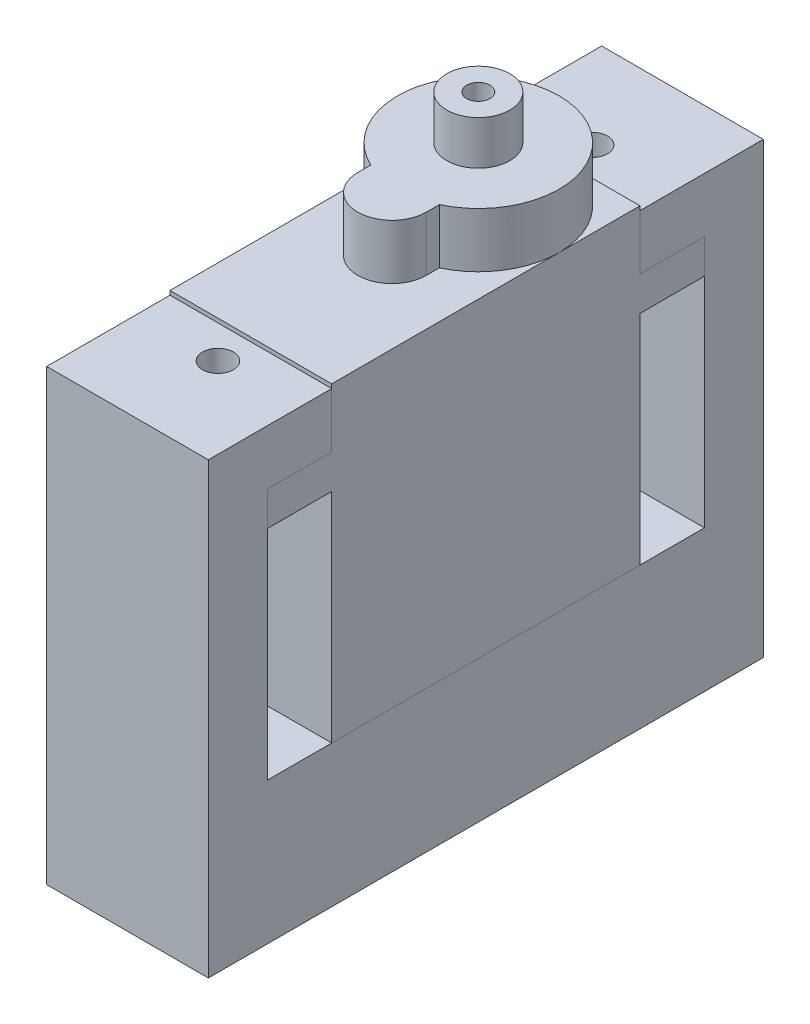
SolidWorks part; units mm, degrees
ref_plane "Plan de face" through (0, 0, 0) normal (0, 0, 1) x (1, 0, 0)
ref_plane "Plan de dessus" through (0, 0, 0) normal (0, 1, 0) x (1, 0, 0)
ref_plane "Plan de droite" through (0, 0, 0) normal (1, 0, 0) x (0, 0, -1)
sketch "Esquisse1" plane through (0, 0, 0) normal (1, 0, 0) x (0, 0, -1)
  line L0 (11.25, 0) -> (-11.25, 0) construction
  line L1 (0, 14.95) -> (0, -14.95) construction
  line L2 (-11.25, -14.95) -> (11.25, -14.95)
  line L3 (11.25, -14.95) -> (11.25, 0.95)
  line L4 (11.25, 0.95) -> (15.95, 0.95)
  line L5 (15.95, 0.95) -> (15.95, 3.45)
  line L6 (15.95, 3.45) -> (11.25, 3.45)
  line L7 (11.25, 3.45) -> (11.25, 7.75)
  line L8 (11.25, 7.75) -> (-11.25, 7.75)
  line L9 (-11.25, 7.75) -> (-11.25, 3.45)
  line L10 (-11.25, 3.45) -> (-15.95, 3.45)
  line L11 (-15.95, 3.45) -> (-15.95, 0.95)
  line L12 (-15.95, 0.95) -> (-11.25, 0.95)
  line L13 (-11.25, 0.95) -> (-11.25, -14.95)
  point P4 (0, 0)
  point P8 (0, 0)
  dimension "D1" = 15.9
  dimension "D2" = 2.5
  dimension "D3" = 4.7
  dimension "D4" = 22.5
  dimension "D5" = 4.7
  dimension "D6" = 4.3
  dimension "D7" = 2.5
  dimension "D8" = 15.9
  dimension "D9" = 22.5
  dimension "D10" = 18.4
  dimension "D11" = 22.7
extrude "Boss.-Extru.1" add sketch "Esquisse1" along normal blind 5.9 and the other way blind 5.9
sketch "Esquisse2" plane through (0, 7.75, 0) normal (0, 1, 0) x (1, 0, 0)
  line L0 (-5.9, 11.25) -> (5.9, 11.25) construction
  line L1 (-5.9, 11.25) -> (5.9, 11.25) construction
  line L2 (-2.5, 0.0058) -> (2.5, 0.0058) construction
  line L3 (0, 5.35) -> (0, -3.45) construction
  line L4 (-2.5, 0.0058) -> (-2.5, -3.45) construction
  line L5 (-2.5, -3.45) -> (2.5, -3.45) construction
  line L6 (2.5, -3.45) -> (2.5, 0.0058) construction
  line L7 (-2.5, -0.95) -> (-2.5, 0.0058)
  line L8 (2.5, -0.95) -> (2.5, 0.0058)
  arc A0 (2.5, 0.0058) -> (-2.5, 0.0058) centre (0, 5.35) ccw
  arc A1 (-2.5, -0.95) -> (2.5, -0.95) centre (0, -0.95) ccw
  point P6 (-2.5, -1.7221)
  point P11 (2.5, -1.7221)
extrude "Boss.-Extru.2" add sketch "Esquisse2" along normal blind 4
sketch "Esquisse3" plane through (0, 3.45, 0) normal (0, 1, 0) x (1, 0, 0)
  line L0 (0, 18.25) -> (0, 11.25) construction
  line L1 (0, 11.25) -> (7.0868, 11.25) construction
  line L2 (0, 15.95) -> (0, 13.65) construction
  line L3 (-5.9, 15.95) -> (5.9, 15.95) construction
  line L4 (-0.65, 15.95) -> (0.65, 15.95) construction
  line L5 (-0.65, 15.95) -> (-0.65, 14.4099)
  line L6 (0.65, 15.95) -> (0.65, 14.4099)
  line L7 (-0.65, 15.95) -> (0.65, 15.95)
  line L8 (0, 0) -> (11.6221, 0) construction
  line L9 (-0.65, -15.95) -> (0.65, -15.95) construction
  line L10 (0, -15.95) -> (0, -13.65) construction
  line L11 (0, -11.25) -> (7.0868, -11.25) construction
  line L12 (0, -18.25) -> (0, -11.25) construction
  line L13 (-0.65, -15.95) -> (0.65, -15.95)
  line L14 (0.65, -15.95) -> (0.65, -14.4099)
  line L15 (-0.65, -15.95) -> (-0.65, -14.4099)
  arc A0 (2.5, 0.0058) -> (-2.5, 0.0058) centre (0, 5.35) ccw construction
  arc A1 (-0.65, 14.4099) -> (0.65, 14.4099) centre (0, 13.65) ccw
  arc A2 (-0.65, -14.4099) -> (0.65, -14.4099) centre (0, -13.65) cw
  point P13 (0, 15.95)
  point P27 (0, -15.95)
extrude "Enlèv. mat.-Extru.1" cut sketch "Esquisse3" against normal up to surface (2.5 mm away) up to face at (0, 0.95, -13.6)
sketch "Esquisse4" plane through (0, 11.75, 0) normal (0, 1, 0) x (1, 0, 0)
  circle A0 centre (0, 5.35) radius 2.3
  circle A1 centre (0, 5.35) radius 0.85
extrude "Boss.-Extru.3" add sketch "Esquisse4" along normal blind 3.2
sketch "Sketch1" plane through (0, 3.45, 0) normal (0, 1, 0) x (1, 0, 0)
  line L0 (5.9, -11.25) -> (-5.9, -11.25)
  line L1 (5.9, -11.25) -> (5.9, -20.25)
  line L2 (-5.9, -11.25) -> (-5.9, -20.25)
  line L3 (5.9, -20.25) -> (-5.9, -20.25)
  circle A0 centre (0, -13.65) radius 1.125
  dimension "D2" = 2.25
  dimension "D1" = 9
extrude "Boss-Extrude1" add sketch "Sketch1" along normal blind 4 separate body
sketch "Sketch3" plane through (0, 3.45, 0) normal (0, -1, 0) x (1, 0, 0)
  line L1 (-5.9, 15.95) -> (5.9, 15.95)
  line L2 (-5.9, 15.95) -> (-5.9, 20.25)
  line L3 (-5.9, 20.25) -> (5.9, 20.25)
  line L4 (5.9, 15.95) -> (5.9, 20.25)
extrude "Boss-Extrude2" add sketch "Sketch3" along normal offset from surface (22.4 mm away) 4 separate body up to face at (0, -14.95, 0) offset beyond the face yes
sketch "Sketch4" plane through (0, -14.95, 0) normal (0, -1, 0) x (1, 0, 0)
  line L0 (-5.9, 0) -> (5.9, 0)
  line L1 (-5.9, 11.25) -> (5.9, 11.25)
  line L2 (-5.9, 11.25) -> (-5.9, -11.25)
  line L3 (-5.9, -11.25) -> (5.9, -11.25)
  line L4 (5.9, 11.25) -> (5.9, -11.25)
sketch "Sketch5" plane through (0, 0, 15.95) normal (0, 0, -1) x (-1, 0, 0)
  line L0 (5.9, -18.95) -> (5.9, 3.45) construction
  line L1 (-5.9, -18.95) -> (5.9, -18.95)
  line L2 (-5.9, -18.95) -> (-5.9, -14.95)
  line L3 (-5.9, -14.95) -> (5.9, -14.95)
  line L4 (5.9, -18.95) -> (5.9, -14.95)
  dimension "D1" = 4
extrude "Boss-Extrude3" add sketch "Sketch5" along normal up to vertex (15.95 mm away) separate body up to point (-5.9, -14.95, 0)
combine bodies "Combine1" operation type add bodies to combine 107 106 105
ref_plane "Plane1" through (0, 0, 0) normal (0, 0, -1) x (-1, 0, 0)
mirror "Mirror3" about plane through (0, 0, 0) normal (0, 0, -1) of "Boss-Extrude1", "Boss-Extrude2", "Boss-Extrude3"
sketch "Sketch6" plane through (0, -18.95, 0) normal (0, -1, 0) x (1, 0, 0)
  line L1 (-5.9, 20.25) -> (5.9, 20.25)
  line L2 (-5.9, 20.25) -> (-5.9, -20.25)
  line L3 (-5.9, -20.25) -> (5.9, -20.25)
  line L4 (5.9, 20.25) -> (5.9, -20.25)
extrude "Boss-Extrude4" add sketch "Sketch6" along normal blind 6.35
sketch "Sketch7" plane through (-5.9, 0, 0) normal (-1, 0, 0) x (0, 0, 1)
  line L0 (0, -25.3) -> (0, -14.95)
  line L1 (20.25, -25.3) -> (-20.25, -25.3) construction
  line L2 (11.25, -14.95) -> (-11.25, -14.95) construction
  line L3 (12.7, -20.125) -> (-12.7, -20.125)
  circle A0 centre (12.7, -20.125) radius 2.2479
  circle A1 centre (-12.7, -20.125) radius 2.2479
  point P9 (0, -20.125)
  dimension "D1" = 4.4958
  dimension "D2" = 25.4
extrude "Cut-Extrude1" [suppressed] cut sketch "Sketch7" against normal through all contours A0 | A1
sketch "Sketch8" [suppressed] plane through (-5.9, 0, 0) normal (-1, 0, 0) x (0, 0, 1)
  line L1 (20.25, -25.3) -> (-20.25, -25.3)
  line L2 (20.25, -25.3) -> (20.25, 7.45)
  line L3 (20.25, 7.45) -> (-20.25, 7.45)
  line L4 (-20.25, -25.3) -> (-20.25, 7.45)
  circle A1 centre (-12.7, -20.125) radius 2.2479
  circle A3 centre (12.7, -20.125) radius 2.2479
  dimension "D1" = 4.4958
  dimension "D2" = 4.4958
extrude "Boss-Extrude5" [suppressed] add sketch "Sketch8" along normal blind 1
sketch "Sketch9" plane through (0, -25.3, 0) normal (0, -1, 0) x (1, 0, 0)
  line L0 (0, -12.7) -> (0, 12.7)
  circle A0 centre (0, -12.7) radius 2.2479
  circle A1 centre (0, 12.7) radius 2.2479
  point P4 (0, 0)
  dimension "D1" = 4.4958
  dimension "D2" = 25.4
extrude "Cut-Extrude2" cut sketch "Sketch9" against normal blind 8 contours A0 | A1 region at (-1.5445, -25.3, 14.2445) region at (1.5445, -25.3, -11.1555)
